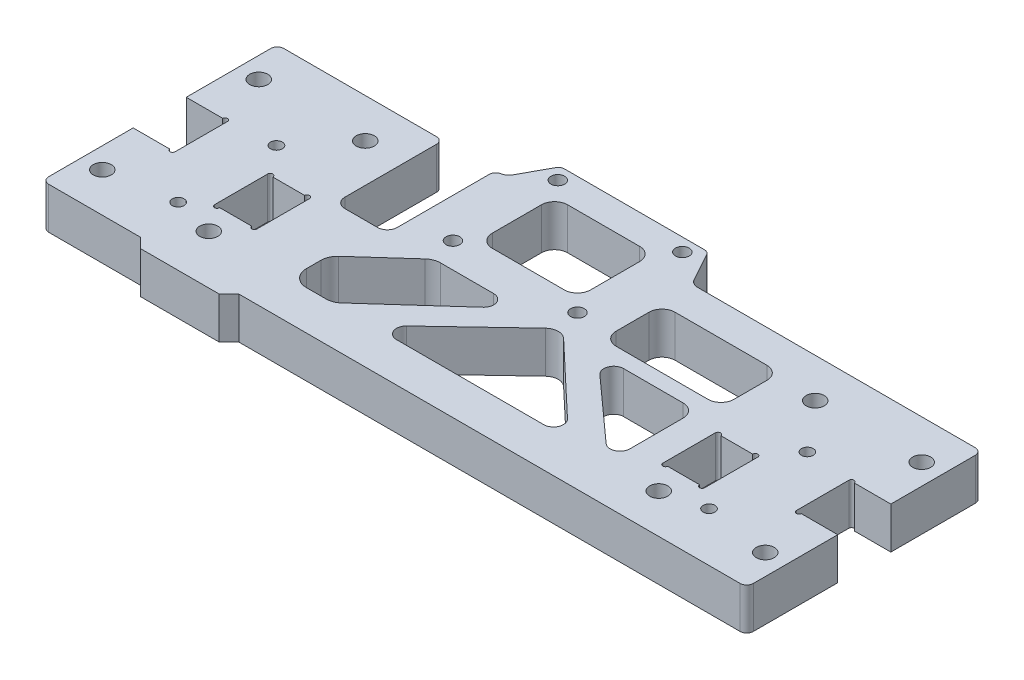
SolidWorks part; units mm, degrees
material "6061 Alloy"
ref_plane "Front Plane" through (0, 0, 0) normal (0, 0, 1) x (1, 0, 0)
ref_plane "Top Plane" through (0, 0, 0) normal (0, 1, 0) x (1, 0, 0)
ref_plane "Right Plane" through (0, 0, 0) normal (1, 0, 0) x (0, 0, -1)
sketch "Sketch1" plane through (0, 0, 0) normal (0, 1, 0) x (1, 0, 0)
  line L0 (107.5, 76.65) -> (107.5, 0) construction
  line L6 (32.7004, 36.1) -> (32.7004, 19.9)
  line L8 (45.6, 36) -> (45.6, 20)
  line L13 (0, 71.75) -> (69.5, 71.75)
  line L14 (69.5, 71.75) -> (75.5, 82.75)
  line L15 (75.5, 82.75) -> (120.5, 82.75)
  line L16 (120.5, 82.75) -> (126.5, 71.75)
  line L17 (126.5, 71.75) -> (215, 71.75)
  line L18 (32.7004, 28) -> (45.6, 28) construction
  line L19 (34.3004, 36.1) -> (44.0063, 36.1)
  line L20 (34.3004, 19.9) -> (44.0063, 19.9)
  line L21 (182.2996, 36.1) -> (182.2996, 19.9)
  line L22 (180.6996, 36.1) -> (170.9937, 36.1)
  line L23 (169.4, 36) -> (169.4, 20)
  line L24 (180.6996, 19.9) -> (170.9937, 19.9)
  line L25 (12.7, 35.875) -> (0, 35.875) construction
  line L29 (12.7, 43.975) -> (12.7, 27.775)
  line L30 (11.1189, 43.975) -> (0, 43.975)
  line L31 (11.1189, 27.775) -> (0, 27.775)
  line L32 (0, 27.775) -> (0, 0)
  line L33 (0, 43.975) -> (0, 71.75)
  line L34 (202.3, 35.875) -> (215, 35.875) construction
  line L35 (215, 43.975) -> (215, 71.75)
  line L36 (215, 27.775) -> (215, 0)
  line L37 (203.8811, 27.775) -> (215, 27.775)
  line L38 (203.8811, 43.975) -> (215, 43.975)
  line L39 (202.3, 43.975) -> (202.3, 27.775)
  line L40 (0, 0) -> (30, 0)
  line L41 (30, 0) -> (33, -3)
  line L42 (33, -3) -> (57, -3)
  line L43 (57, -3) -> (60, 0)
  line L44 (60, 0) -> (215, 0)
  circle A0 centre (38.85, 59.75) radius 2.75
  circle A5 centre (38.85, 12) radius 2.75
  circle A6 centre (176.15, 59.75) radius 2.75
  circle A7 centre (176.15, 12) radius 2.75
  arc A8 (32.7004, 36.1) -> (34.3004, 36.1) centre (33.5004, 36.1) cw
  arc A9 (45.6, 36) -> (44.0063, 36.1) centre (44.8, 36) ccw
  arc A10 (32.7004, 19.9) -> (34.3004, 19.9) centre (33.5004, 19.9) ccw
  arc A11 (45.6, 20) -> (44.0063, 19.9) centre (44.8, 20) cw
  arc A12 (182.2996, 19.9) -> (180.6996, 19.9) centre (181.4996, 19.9) cw
  arc A13 (182.2996, 36.1) -> (180.6996, 36.1) centre (181.4996, 36.1) ccw
  arc A14 (169.4, 36) -> (170.9937, 36.1) centre (170.2, 36) cw
  arc A15 (169.4, 20) -> (170.9937, 19.9) centre (170.2, 20) ccw
  circle A16 centre (6.35, 12) radius 2.75
  circle A17 centre (6.35, 59.75) radius 2.75
  arc A18 (12.7, 27.775) -> (11.1189, 27.775) centre (11.9095, 27.8976) cw
  arc A19 (12.7, 43.975) -> (11.1189, 43.975) centre (11.9095, 43.8524) ccw
  arc A20 (202.3, 43.975) -> (203.8811, 43.975) centre (203.0905, 43.8524) cw
  arc A21 (202.3, 27.775) -> (203.8811, 27.775) centre (203.0905, 27.8976) ccw
  circle A22 centre (208.65, 59.75) radius 2.75
  circle A23 centre (208.65, 12) radius 2.75
  dimension "D12" = 5.5
  dimension "D16" = 5.5
  dimension "D17" = 0.8
  dimension "D18" = 0.8
  dimension "D19" = 0.8
  dimension "D20" = 0.8
  dimension "D21" = 5.5
  dimension "D22" = 5.5
  dimension "D27" = 0.8
  dimension "D1" = 215
  dimension "D2" = 71.75
  dimension "D5" = 61.9
  dimension "D6" = 12.9
  dimension "D4" = 11
  dimension "D7" = 6
  dimension "D8" = 38
  dimension "D10" = 45
  dimension "D11" = 16.2
  dimension "D14" = 6
  dimension "D13" = 12
  dimension "D25" = 16.2
  dimension "D3" = 12
  dimension "D23" = 16.2
  dimension "D26" = 12.7
  dimension "D9" = 3
  dimension "D15" = 30
  dimension "D24" = 30
  dimension "D28" = 3
  dimension "D29" = 35.875
extrude "Boss-Extrude1" add sketch "Sketch1" along normal blind 12.7
sketch "Sketch2" plane through (0, 12.7, 0) normal (0, 1, 0) x (1, 0, 0)
  line L1 (50.6, 85.2461) -> (66.6, 85.2461)
  line L2 (50.6, 85.2461) -> (50.6, 38.75)
  line L3 (50.6, 38.75) -> (66.6, 38.75)
  line L4 (66.6, 85.2461) -> (66.6, 38.75)
  line L5 (45.6, 20) -> (45.6, 36) construction
  line L12 (69.5, 71.75) -> (0, 71.75) construction
  dimension "D1" = 5
  dimension "D2" = 16
  dimension "D3" = 33
extrude "Cut-Extrude1" cut sketch "Sketch2" against normal through all
sketch "Sketch3" plane through (0, 12.7, 0) normal (0, 1, 0) x (1, 0, 0)
  line L1 (66.6, 38.75) -> (66.6, 71.75) construction
  line L2 (120.5, 82.75) -> (75.5, 82.75) construction
  circle A0 centre (78.6, 78.75) radius 2.1
  circle A1 centre (78.6, 46.75) radius 2.1
  circle A2 centre (116.6, 78.75) radius 2.1
  circle A3 centre (116.6, 46.75) radius 2.1
  dimension "D2" = 4.2
  dimension "D5" = 4.2
  dimension "D8" = 32
  dimension "D1" = 4
  dimension "D3" = 12
  dimension "D4" = 32
  dimension "D7" = 38
  dimension "D6" = 2
extrude "Cut-Extrude2" cut sketch "Sketch3" against normal through all
sketch "Sketch5" plane through (0, 12.7, 0) normal (0, 1, 0) x (1, 0, 0)
  line L3 (98.7821, 39) -> (82.5187, 39)
  line L11 (78.0261, 13.2835) -> (100.789, 33.7701)
  line L12 (66.6, 38.75) -> (66.6, 71.75) construction
  line L13 (115.8513, 37.7761) -> (94.0759, 17.1795)
  line L14 (118.6, 40.376) -> (118.6, 12) construction
  line L15 (96.1374, 12) -> (141.0626, 12)
  line L16 (121.3487, 37.7761) -> (143.1241, 17.1795)
  line L17 (138.4179, 39) -> (156.6, 39)
  line L18 (155.5931, 16.5062) -> (136.411, 33.7701)
  line L19 (160.6, 35) -> (160.6, 18.7361)
  line L20 (120.5, 82.75) -> (75.5, 82.75) construction
  line L21 (86.6, 73.75) -> (108.6, 73.75)
  line L22 (82.6, 69.75) -> (82.6, 54.75)
  line L23 (86.6, 50.75) -> (108.6, 50.75)
  line L24 (112.6, 69.75) -> (112.6, 54.75)
  line L25 (215, 71.75) -> (126.5, 71.75) construction
  line L26 (131.4, 61.75) -> (159.4, 61.75)
  line L27 (127.4, 57.75) -> (127.4, 47.75)
  line L28 (131.4, 43.75) -> (159.4, 43.75)
  line L29 (163.4, 57.75) -> (163.4, 47.75)
  line L30 (79.1739, 37.7165) -> (65.279, 25.2111)
  line L31 (169.4, 36) -> (169.4, 20) construction
  line L32 (63.6239, 21.4947) -> (63.6239, 17)
  line L33 (68.6239, 12) -> (74.6813, 12)
  arc A0 (121.3487, 37.7761) -> (115.8513, 37.7761) centre (118.6, 34.8701) ccw
  arc A1 (160.6, 35) -> (156.6, 39) centre (156.6, 35) ccw
  arc A3 (112.6, 69.75) -> (108.6, 73.75) centre (108.6, 69.75) ccw
  arc A4 (108.6, 50.75) -> (112.6, 54.75) centre (108.6, 54.75) ccw
  arc A5 (82.6, 54.75) -> (86.6, 50.75) centre (86.6, 54.75) ccw
  arc A6 (82.6, 69.75) -> (86.6, 73.75) centre (86.6, 69.75) cw
  arc A7 (155.5931, 16.5062) -> (160.6, 18.7361) centre (157.6, 18.7361) ccw
  arc A8 (136.411, 33.7701) -> (138.4179, 39) centre (138.4179, 36) cw
  arc A10 (141.0626, 12) -> (143.1241, 17.1795) centre (141.0626, 15) ccw
  arc A11 (96.1374, 12) -> (94.0759, 17.1795) centre (96.1374, 15) cw
  arc A12 (100.789, 33.7701) -> (98.7821, 39) centre (98.7821, 36) ccw
  arc A13 (163.4, 57.75) -> (159.4, 61.75) centre (159.4, 57.75) ccw
  arc A14 (159.4, 43.75) -> (163.4, 47.75) centre (159.4, 47.75) ccw
  arc A15 (127.4, 47.75) -> (131.4, 43.75) centre (131.4, 47.75) ccw
  arc A16 (127.4, 57.75) -> (131.4, 61.75) centre (131.4, 57.75) cw
  arc A17 (79.1739, 37.7165) -> (82.5187, 39) centre (82.5187, 34) cw
  arc A18 (63.6239, 21.4947) -> (65.279, 25.2111) centre (68.6239, 21.4947) cw
  arc A19 (68.6239, 12) -> (63.6239, 17) centre (68.6239, 17) cw
  arc A20 (74.6813, 12) -> (78.0261, 13.2835) centre (74.6813, 17) ccw
  point P25 (160.6, 39)
  point P26 (0, 0)
  point P33 (112.6, 50.75)
  point P36 (82.6, 50.75)
  point P39 (82.6, 73.75)
  point P42 (160.6, 12)
  point P45 (130.6, 39)
  point P48 (76.6, 12)
  point P51 (148.6, 12)
  point P54 (88.6, 12)
  point P57 (106.6, 39)
  point P68 (163.4, 61.75)
  point P71 (163.4, 43.75)
  point P76 (127.4, 61.75)
  dimension "D11" = 4
  dimension "D12" = 3
  dimension "D13" = 3
  dimension "D14" = 3
  dimension "D19" = 4
  dimension "D2" = 5
  dimension "D4" = 5
  dimension "D3" = 12
  dimension "D6" = 30
  dimension "D7" = 9
  dimension "D8" = 16
  dimension "D9" = 23
  dimension "D10" = 30
  dimension "D15" = 10
  dimension "D16" = 18
  dimension "D17" = 6
  dimension "D18" = 36
extrude "Cut-Extrude3" cut sketch "Sketch5" against normal through all
fillet "Fillet1" radius 3 4 edges at (69.5, 6.35, -71.75) (66.6, 6.35, -38.75) (50.6, 6.35, -38.75) (126.5, 6.35, -71.75)
fillet "Fillet2" radius 2 8 edges at (215, 6.35, -71.75) (120.5, 6.35, -82.75) (75.5, 6.35, -82.75) (50.6, 6.35, -71.75) (66.6, 6.35, -71.75) (0, 6.35, -71.75) (215, 6.35, 0) (0, 6.35, 0)
sketch "Sketch6" plane through (0, 12.7, 0) normal (0, 1, 0) x (1, 0, 0)
  line L0 (60, 0) -> (213, 0) construction
  line L1 (107.5, 92.584) -> (107.5, -38.973) construction
  line L2 (215, 2) -> (215, 27.775) construction
  circle A0 centre (188.5, 45) radius 1.8
  circle A1 centre (176.15, 59.75) radius 2.75 construction
  circle A2 centre (188.5, 15) radius 1.8
  circle A3 centre (26.5, 45) radius 1.8
  circle A4 centre (26.5, 15) radius 1.8
  dimension "D2" = 3.6
  dimension "D5" = 3.6
  dimension "D1" = 12.35
  dimension "D3" = 45
  dimension "D4" = 15
  dimension "D6" = 107.5
extrude "Cut-Extrude4" cut sketch "Sketch6" against normal through all
equation "\"DriveMotorLength\"= 90mm"
equation "\"DriveMotorGap\"= 10mm"
equation "\"AluminumThickness\"= 0.5in"
equation "\"ChassisWidth\"= ( \"DriveMotorLength\" + \"AluminumThickness\" ) * 2 + \"DriveMotorGap\""
equation "\"RepeatMagnumHoleWidth\"= 19.05mm"
equation "\"MortiseWidth\"= 16mm"
equation "\"ChassisScrewThruHole\"= 5.5mm"
equation "\"D11@Sketch1\"=\"MortiseSlotWidth\""
equation "\"D12@Sketch1\"=\"ChassisScrewThruHole\""
equation "\"D16@Sketch1\"=\"ChassisScrewThruHole\""
equation "\"MortiseSlotWidth\"= 16.2mm"
equation "\"Dogbone\"= 0.8mm"
equation "\"D17@Sketch1\"=\"Dogbone\""
equation "\"D18@Sketch1\"=\"Dogbone\""
equation "\"D19@Sketch1\"=\"Dogbone\""
equation "\"D20@Sketch1\"=\"Dogbone\""
equation "\"D21@Sketch1\"=\"ChassisScrewThruHole\""
equation "\"D22@Sketch1\"=\"ChassisScrewThruHole\""
equation "\"D27@Sketch1\"=\"Dogbone\""
equation "\"D23@Sketch1\"=\"MortiseSlotWidth\""
equation "\"D25@Sketch1\"=\"MortiseSlotWidth\""
